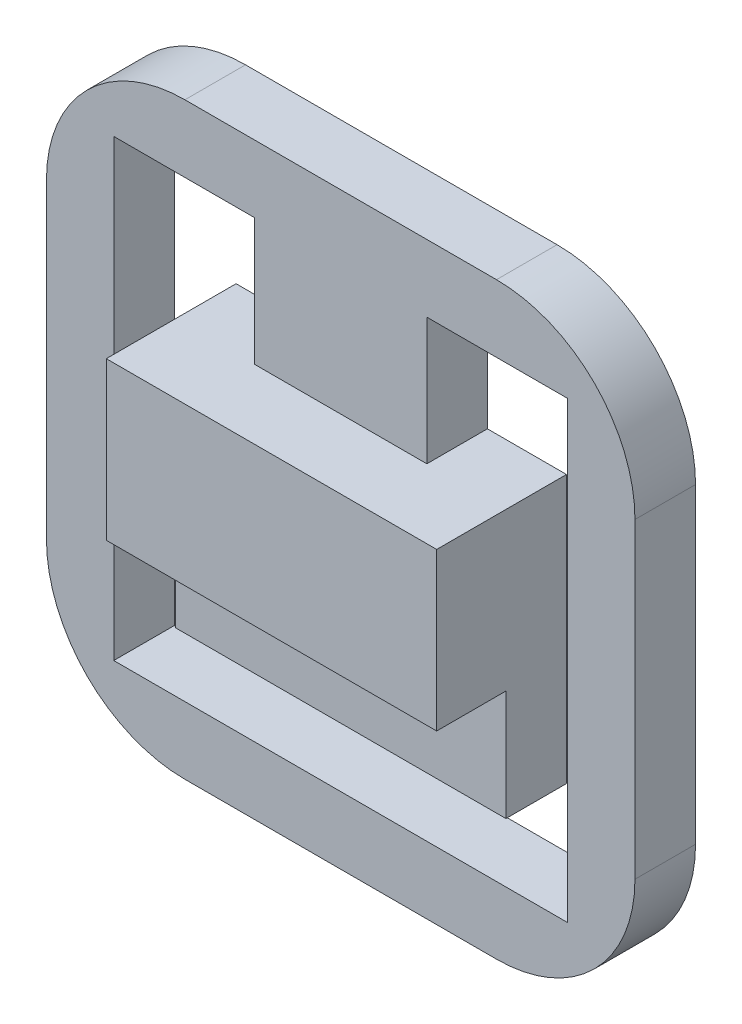
SolidWorks part; units mm, degrees
ref_plane "Front Plane" through (0, 0, 0) normal (0, 0, 1) x (1, 0, 0)
ref_plane "Top Plane" through (0, 0, 0) normal (0, 1, 0) x (1, 0, 0)
ref_plane "Right Plane" through (0, 0, 0) normal (1, 0, 0) x (0, 0, -1)
sketch "Sketch2" plane through (0, 0, 0) normal (0, 0, 1) x (1, 0, 0)
  line L4 (-17, 17) -> (17, 17)
  line L5 (-17, 17) -> (-17, -17)
  line L6 (17, 17) -> (17, -17)
  line L9 (-17, -17) -> (17, -17)
  line L10 (-17, 17) -> (17, -17) construction
  line L11 (17, 17) -> (-17, -17) construction
  line L12 (-13.1124, 13.1124) -> (13.1124, 13.1124)
  line L13 (-13.1124, 13.1124) -> (-13.1124, -13.1124)
  line L14 (13.1124, 13.1124) -> (13.1124, -13.1124)
  line L15 (-13.1124, -13.1124) -> (13.1124, -13.1124)
  line L16 (-13.1124, 13.1124) -> (13.1124, -13.1124) construction
  line L17 (13.1124, 13.1124) -> (-13.1124, -13.1124) construction
  line L18 (-4.9762, 13.1124) -> (-4.9762, 5.775)
  line L19 (-4.9762, 5.775) -> (-9.5441, 5.775)
  line L20 (-9.5441, 5.775) -> (-9.5441, -9.6914)
  line L21 (-9.5441, -9.6914) -> (9.5441, -9.6914)
  line L22 (9.5441, -9.6914) -> (9.5441, 5.775)
  line L23 (9.5441, 5.775) -> (4.9762, 5.775)
  line L24 (4.9762, 5.775) -> (4.9762, 13.1124)
  line L25 (0, 17) -> (0, -17) construction
  point P1 (0, 0)
  point P2 (0, 0)
  point P21 (0, -33.1126)
  point P22 (-10.5394, 10.5394)
  point P23 (-4.5238, 5.775)
  point P24 (-13.1124, -13.1124)
  dimension "D1" = 34
extrude "Boss-Extrude1" add sketch "Sketch2" along normal blind 3.5 contours L5 L9 L6 L4 L15 L13 L12 L14 | L23 L24 L12 L18 L19 L20 L21 L22 region at (0, 16.5192, 0) region at (0, 0.3029, 0)
sketch "Sketch4" plane through (0, 0, 3.5) normal (0, 0, 1) x (1, 0, 0)
  line L0 (9.5441, -9.6914) -> (9.5441, 5.775) construction
  line L1 (-9.5441, 5.775) -> (9.5441, 5.775)
  line L2 (-9.5441, 5.775) -> (-9.5441, -3.3108)
  line L3 (-9.5441, -3.3108) -> (9.5441, -3.3108)
  line L4 (9.5441, 5.775) -> (9.5441, -3.3108)
extrude "Boss-Extrude2" add sketch "Sketch4" along normal blind 4
fillet "Fillet1" radius 8 4 edges at (17, -17, 1.75) (-17, -17, 1.75) (-17, 17, 1.75) (17, 17, 1.75)
